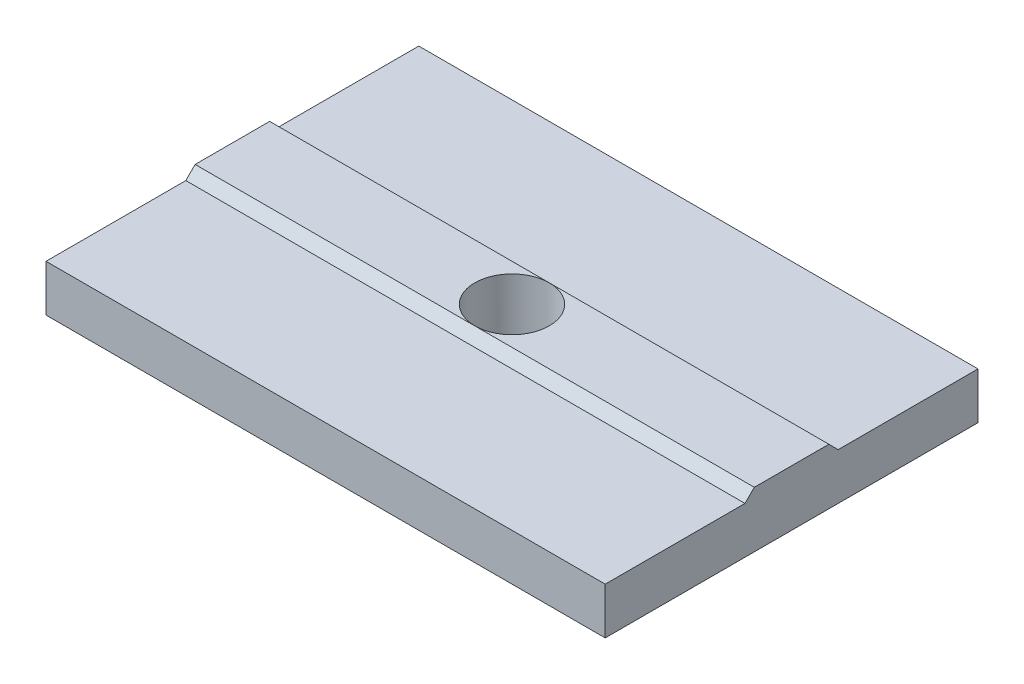
SolidWorks part; units mm, degrees
ref_plane "Płaszczyzna przednia" through (0, 0, 0) normal (0, 0, 1) x (1, 0, 0)
ref_plane "Płaszczyzna górna" through (0, 0, 0) normal (0, 1, 0) x (1, 0, 0)
ref_plane "Płaszczyzna prawa" through (0, 0, 0) normal (1, 0, 0) x (0, 0, -1)
sketch "Szkic1" plane through (0, 0, 0) normal (0, 1, 0) x (1, 0, 0)
  line L1 (30, -20) -> (-30, -20)
  line L2 (30, -20) -> (30, 20)
  line L3 (30, 20) -> (-30, 20)
  line L4 (-30, -20) -> (-30, 20)
  line L5 (30, -20) -> (-30, 20) construction
  line L6 (30, 20) -> (-30, -20) construction
  point P0 (0, 0)
  dimension "D1" = 40
  dimension "D2" = 60
extrude "Dodanie-wyciągnięcie1" add sketch "Szkic1" along normal blind 5
sketch "Szkic2" plane through (0, 0, 0) normal (0, 1, 0) x (1, 0, 0)
  line L0 (-30, 20) -> (-30, -20) construction
  line L1 (30, -5) -> (-30, -5)
  line L2 (30, -5) -> (30, 5)
  line L3 (30, 5) -> (-30, 5)
  line L4 (-30, -5) -> (-30, 5)
  line L5 (30, -5) -> (-30, 5) construction
  line L6 (30, 5) -> (-30, -5) construction
  point P0 (0, 0)
  dimension "D1" = 10
extrude "Dodanie-wyciągnięcie2" add sketch "Szkic2" along normal blind 6
chamfer "Sfazowanie1" distance 1 angle 45 2 edges at (0, 6, -5) (0, 6, 5)
sketch "Szkic3" plane through (0, 0, 0) normal (0, 1, 0) x (1, 0, 0)
  circle A0 centre (0, 0) radius 4
  dimension "D1" = 8
extrude "Wytnij-wyciągnięcie1" cut sketch "Szkic3" against normal through all both and the other way through all
